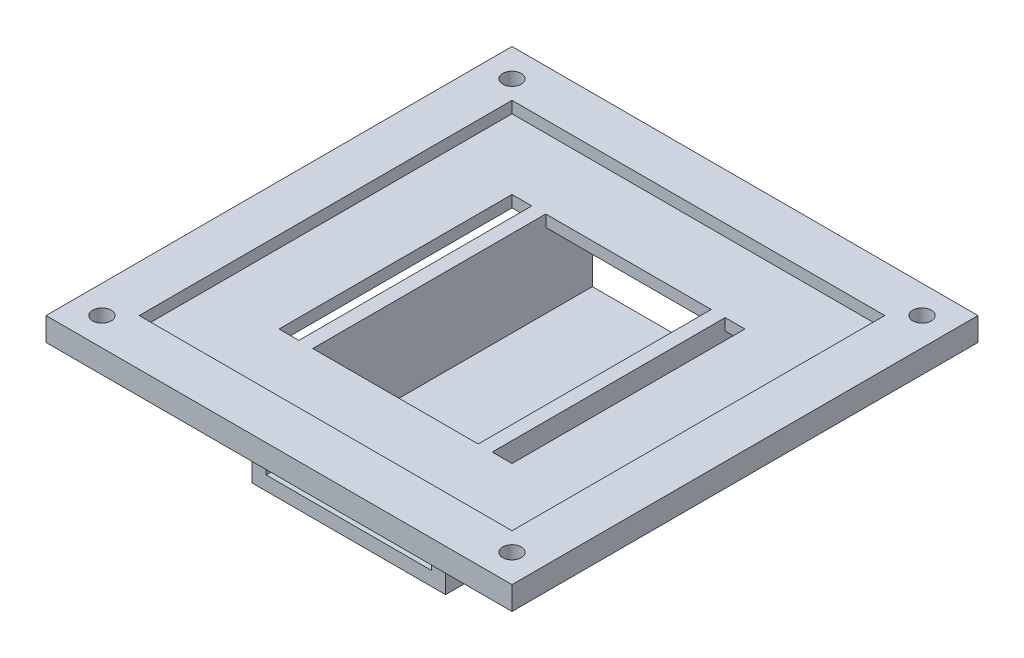
SolidWorks part; units mm, degrees
ref_plane "정면" through (0, 0, 0) normal (0, 0, 1) x (1, 0, 0)
ref_plane "윗면" through (0, 0, 0) normal (0, 1, 0) x (1, 0, 0)
ref_plane "우측면" through (0, 0, 0) normal (1, 0, 0) x (0, 0, -1)
sketch "스케치2" plane through (0, 0, 0) normal (0, 1, 0) x (1, 0, 0)
  line L1 (50, 50) -> (-50, 50)
  line L2 (50, 50) -> (50, -50)
  line L3 (50, -50) -> (-50, -50)
  line L4 (-50, 50) -> (-50, -50)
  line L5 (50, 50) -> (-50, -50) construction
  line L6 (50, -50) -> (-50, 50) construction
  line L7 (-25, 25) -> (25, 25)
  line L8 (-25, 25) -> (-25, -25)
  line L9 (-25, -25) -> (25, -25)
  line L10 (25, 25) -> (25, -25)
  line L11 (-25, 25) -> (25, -25) construction
  line L12 (-25, -25) -> (25, 25) construction
  circle A0 centre (-44, 44) radius 2
  circle A1 centre (44, 44) radius 2
  circle A2 centre (-44, -44) radius 2
  circle A3 centre (44, -44) radius 2
  point P0 (0, 0)
  point P6 (0, 0)
  dimension "D5" = 4
  dimension "D1" = 100
  dimension "D2" = 100
  dimension "D3" = 50
  dimension "D4" = 50
  dimension "D6" = 6
  dimension "D7" = 6
  dimension "D8" = 6
  dimension "D9" = 6
extrude "보스-돌출1" add sketch "스케치2" along normal mid plane 5
sketch "스케치6" plane through (0, 0, 0) normal (0, 0, 1) x (1, 0, 0)
  line L0 (0, 0) -> (50000, 0) construction
  line L2 (0, 0) -> (0, -50000) construction
  line L3 (-20.75, 0) -> (-20.75, -21.5)
  line L4 (-20.75, -21.5) -> (20.75, -21.5)
  line L6 (17.75, -18.5) -> (-17.75, -18.5)
  line L7 (-17.75, -18.5) -> (-17.75, 0)
  line L8 (-17.75, 0) -> (-20.75, 0)
  line L9 (17.75, 0) -> (20.75, 0)
  line L10 (17.75, -18.5) -> (17.75, 0)
  line L11 (20.75, 0) -> (20.75, -21.5)
  line L12 (-50, -2.5) -> (50, -2.5) construction
  point P14 (0, -18.5)
  point P15 (0, -21.5)
  dimension "D1" = 35.5
  dimension "D2" = 3
  dimension "D3" = 16
  dimension "D4" = 3
extrude "보스-돌출4" add sketch "스케치6" along normal mid plane 70
sketch "스케치7" plane through (0, 0, 0) normal (0, 1, 0) x (1, 0, 0)
  line L1 (-40, 40) -> (40, 40)
  line L2 (-40, 40) -> (-40, -40)
  line L3 (-40, -40) -> (40, -40)
  line L4 (40, 40) -> (40, -40)
  line L5 (-40, 40) -> (40, -40) construction
  line L6 (-40, -40) -> (40, 40) construction
  point P0 (0, 0)
  dimension "D1" = 80
  dimension "D2" = 80
extrude "컷-돌출1" cut sketch "스케치7" along normal blind 10
